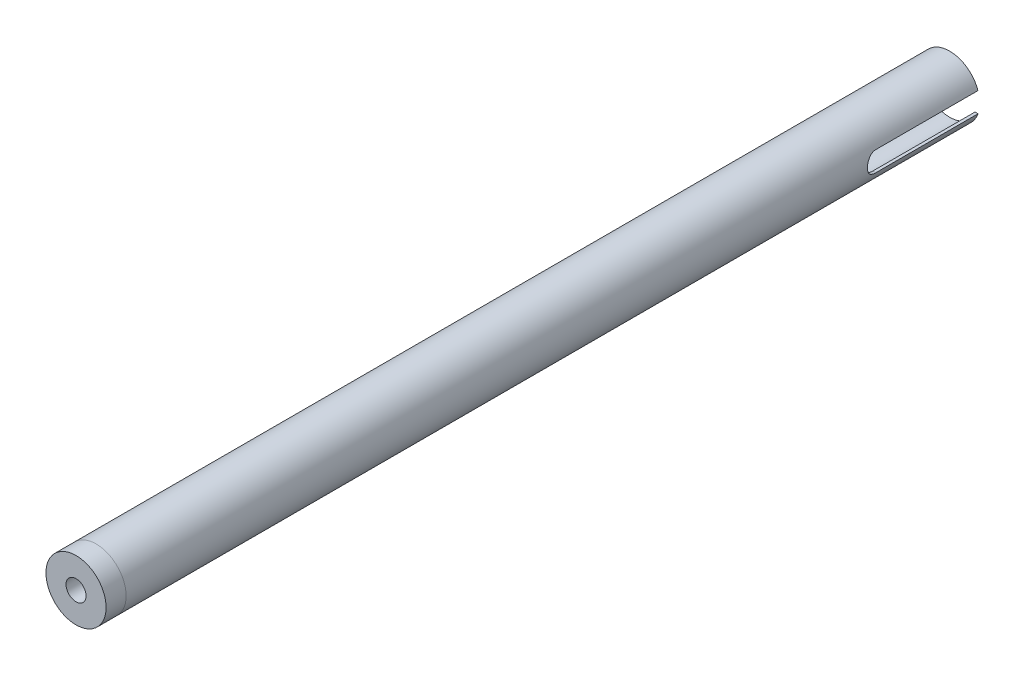
SolidWorks part; units mm, degrees
material "AISI 4130 Steel, annealed at 865C"
ref_plane "Front Plane" through (0, 0, 0) normal (0, 0, 1) x (1, 0, 0)
ref_plane "Top Plane" through (0, 0, 0) normal (0, 1, 0) x (1, 0, 0)
ref_plane "Right Plane" through (0, 0, 0) normal (1, 0, 0) x (0, 0, -1)
sketch "Axis" plane through (0, 0, 0) normal (0, 1, 0) x (1, 0, 0)
  line L0 (0, 0) -> (0, 276.704) construction
  line L1 (0, 0) -> (0, -21.9075) construction
  line L2 (0, 276.704) -> (-9.525, 276.704) construction
  line L4 (0, 301.7331) -> (-10.414, 274.368) construction
  dimension "D1" = 21.9075
  dimension "D2" = 9.525
sketch "Sketch1" plane through (0, 0, 0) normal (0, 0, 1) x (1, 0, 0)
  line L0 (-9.525, 0) -> (9.525, 0) construction
  line L1 (-8.9803, 3.175) -> (8.9803, 3.175)
  line L2 (-8.9803, -3.175) -> (8.9803, -3.175)
  circle A0 centre (0, 0) radius 9.525
  circle A1 centre (0, 0) radius 8.636
  circle A2 centre (0, 0) radius 3.175
  dimension "D1" = 19.05
  dimension "D3" = 6.35
  dimension "D2" = 0.889
  dimension "D4" = 6.35
extrude "Threaded insert 1-1" add sketch "Sketch1" against normal blind 6.35 contours A2 L1 A1 | A1 L1 A0 | A2 L0 A1 L1 | A1 L0 A0 L1 | L0 A1 L2 A0 | L0 A2 L2 A1 | A2 L2 A1 | A1 L2 A0 | L0 A1 L2 A2 | L0 A0 L2 A1 | A0 L0 A1 L1 | A1 L0 A2 L1 region at (5.4259, 1.6615, 0) region at (5.4259, -1.6615, 0) region at (8.8881, 1.6046, 0) region at (8.8881, -1.6046, 0) region at (-5.4259, -1.6615, 0) region at (-5.4259, 1.6615, 0) region at (0, 5.4321, 0) region at (0, -5.4321, 0) region at (0, 8.8265, 0) region at (8.5057, -3.3655, 0) region at (-8.8881, -1.6046, 0) region at (-8.8881, 1.6046, 0)
extrude "Threaded insert 1-2" add sketch "Sketch1<3>" against normal blind 6.35 from surface contours A2 L1 A1 | A2 L0 A1 L1 | L0 A2 L2 A1 | A2 L2 A1 | L0 A1 L2 A2 | A1 L0 A2 L1 region at (5.4259, 1.6615, 0) region at (5.4259, -1.6615, 0) region at (-5.4259, -1.6615, 0) region at (-5.4259, 1.6615, 0) region at (0, 5.4321, 0) region at (0, -5.4321, 0) starting at face at (9.525, 0, -6.35)
sketch "Sketch1<3>" plane through (0, 0, 0) normal (0, 0, 1) x (1, 0, 0) same geometry as "Sketch1"
extrude "A-arm tube" add sketch "Sketch1<4>" against normal up to vertex (276.704 mm away) from surface separate body contours A1 L1 A0 | A1 L0 A0 L1 | L0 A1 L2 A0 | A1 L2 A0 | L0 A0 L2 A1 | A0 L0 A1 L1 region at (8.8881, 1.6046, 0) region at (8.8881, -1.6046, 0) region at (0, 8.8265, 0) region at (8.5057, -3.3655, 0) region at (-8.8881, -1.6046, 0) region at (-8.8881, 1.6046, 0) up to point (0, 0, -276.704) starting at face at (8.636, 0, -6.35)
sketch "Sketch1<4>" plane through (0, 0, 0) normal (0, 0, 1) x (1, 0, 0) same geometry as "Sketch1"
extrude "Apex slot" cut sketch "Sketch1<5>" along normal blind 35.56 from surface contours A0 L0 A1 L1 | L0 A0 L2 A1 | A1 L0 A0 L1 | L0 A1 L2 A0 region at (8.8881, 1.6046, 0) region at (8.8881, -1.6046, 0) region at (-8.8881, -1.6046, 0) region at (-8.8881, 1.6046, 0) starting at face at (8.636, 0, -276.704)
sketch "Sketch1<5>" plane through (0, 0, 0) normal (0, 0, 1) x (1, 0, 0) same geometry as "Sketch1"
fillet "Fillet1" radius 3.175 4 edges at (-8.5057, 3.175, -241.144) (-8.5057, -3.175, -241.144) (8.5057, -3.175, -241.144) (8.5057, 3.175, -241.144)
equation "\"tube diameter\"= 3 / 4"
equation "\"tube thickness\"= .035"
equation "\"apex thickness\"= .25"
equation "\"tube slot\"= 1.4"
equation "\"D1@Sketch1\"=\"tube diameter\""
equation "\"D2@Sketch1\"=\"tube thickness\""
equation "\"threaded insert hole\"= 1 / 4"
equation "\"D3@Sketch1\"=\"threaded insert hole\""
equation "\"D4@Sketch1\"=\"apex thickness\""
equation "\"D1@Apex slot\" = \"tube slot\""
equation "\"D1@Fillet1\"=\"apex thickness\"/2"
equation "\"D2@Axis\"=\"tube diameter\"/2"
